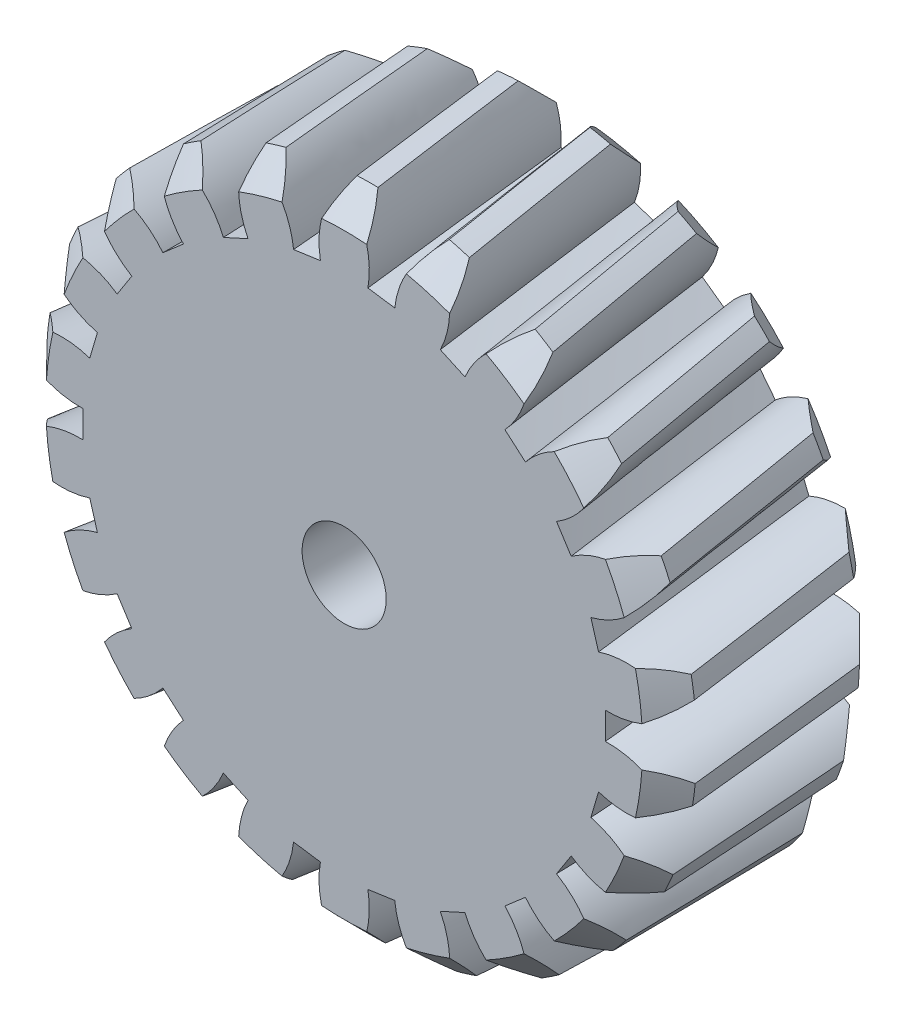
SolidWorks part; units mm, degrees
ref_plane "Front Plane" through (0, 0, 0) normal (1, 0, 0) x (0, 1, 0)
ref_plane "Top Plane" through (0, 0, 0) normal (0, 0, 1) x (0, 1, 0)
ref_plane "Right Plane" through (0, 0, 0) normal (0, 1, 0) x (-1, 0, 0)
sketch "Sketch5" plane through (0, 0, 0) normal (0, 0, 1) x (0, 1, 0)
  circle A0 centre (0, 0) radius 12
  dimension "D1" = 24
extrude "Boss-Extrude1" add sketch "Sketch5" along normal blind 8
chamfer "Chamfer1" distance 1 angle 45 2 edges at (12, 0, 8) (12, 0, 0)
sketch "Sketch9" plane through (0, 0, 8) normal (0, 0, 1) x (1, 0, 0)
  circle A0 centre (0, 0) radius 12 construction
  circle A1 centre (0, 0) radius 12
curve "Helix/Spiral1" pitch 544.9591 height 20 radius 12 left hand yes centre (0, 0, 8) axis (0, 0, -1) start towards (-1, 0, 0)
sketch "Sketch10" plane through (0, 0, 8) normal (0, 0, 1) x (1, 0, 0)
  line L0 (0, 0) -> (31, 0) construction
  line L1 (9.6266, 0.5) -> (9.6266, -0.5)
  circle A0 centre (0, 0) radius 12 construction
  arc A1 (11.9266, -1.325) -> (11.9266, 1.325) centre (0, 0) ccw
  arc A2 (9.6266, 0.5) -> (11.9266, 1.325) centre (9.7416, 3.798) ccw
  arc A3 (9.6266, -0.5) -> (11.9266, -1.325) centre (9.7416, -3.798) cw
  point P9 (9.6266, 0)
  dimension "D2" = 2.65
  dimension "D4" = 3.3
  dimension "D1" = 1
  dimension "D3" = 2.3
sweep "Cut-Sweep1" cut profiles "Sketch10" path "Helix/Spiral1" align with end faces yes
pattern_circular "CirPattern1" count 22 over 360 about axis through (0, 0, 8) along (0, 0, -1) of "Cut-Sweep1" reverse direction yes
sketch "Sketch11" plane through (0, 0, 0) normal (0, 0, 1) x (0, 1, 0)
  circle A0 centre (0, 0) radius 2.95
  dimension "D1" = 5.9
extrude "Cut-Extrude1" cut sketch "Sketch11" along normal blind 2.75
sketch "Sketch12" plane through (0, 0, 0) normal (0, 0, 1) x (0, 1, 0)
  circle A0 centre (0, 0) radius 1.55
  dimension "D1" = 3.1
extrude "Cut-Extrude2" cut sketch "Sketch12" along normal blind 10
